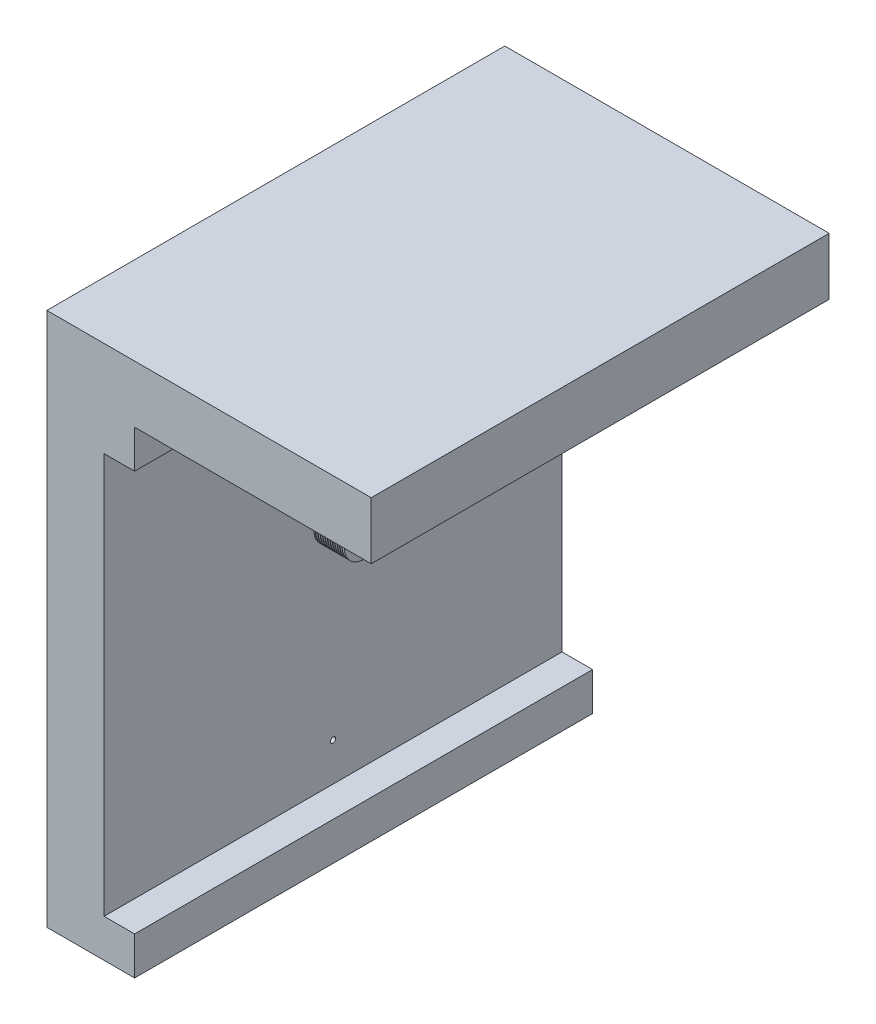
SolidWorks part; units mm, degrees
ref_plane "Front Plane" through (0, 0, 0) normal (0, 0, 1) x (1, 0, 0)
ref_plane "Top Plane" through (0, 0, 0) normal (0, 1, 0) x (1, 0, 0)
ref_plane "Right Plane" through (0, 0, 0) normal (1, 0, 0) x (0, 0, -1)
sketch "Sketch1" plane through (0, 0, 0) normal (0, 0, 1) x (1, 0, 0)
  line L0 (0, 0) -> (0, -70)
  line L1 (0, 0) -> (42.5, 0)
  line L2 (0, -70) -> (7.5, -70)
  line L3 (42.5, 0) -> (42.5, -7.5)
  line L4 (42.5, -7.5) -> (7.5, -7.5)
  line L5 (7.5, -7.5) -> (7.5, -70)
extrude "Boss-Extrude1" add sketch "Sketch1" along normal blind 60
sketch "Sketch3" plane through (0, 0, 0) normal (-1, 0, 0) x (0, 0, 1)
  line L1 (60, 0) -> (60, -70) construction
  line L2 (60, -60) -> (0, -60) construction
  line L3 (0, 0) -> (0, -70) construction
  circle A0 centre (30, -60) radius 0.35
extrude "Cut-Extrude1" cut sketch "Sketch3" against normal through all contours A0
sketch "Sketch5" plane through (7.5, 0, 0) normal (1, 0, 0) x (0, 0, -1)
  line L0 (-60, -70) -> (-60, -7.5) construction
  line L1 (0, -70) -> (-60, -70)
  line L2 (0, -70) -> (0, -65)
  line L3 (0, -65) -> (-60, -65)
  line L4 (-60, -70) -> (-60, -65)
  line L5 (0, -70) -> (0, -7.5) construction
  line L6 (-60, -7.5) -> (0, -7.5)
  line L7 (-60, -7.5) -> (-60, -12.5)
  line L8 (-60, -12.5) -> (0, -12.5)
  line L9 (0, -7.5) -> (0, -12.5)
  dimension "D1" = 5
  dimension "D2" = 5
extrude "Boss-Extrude2" add sketch "Sketch5" along normal blind 4
sketch "Sketch6" plane through (7.5, 0, 0) normal (1, 0, 0) x (0, 0, -1)
  line L0 (-30, -60) -> (-30, -35) construction
  circle A0 centre (-30, -35) radius 2.5
extrude "Boss-Extrude3" add sketch "Sketch6" along normal blind 4
thread "Thread1" pitch 0.3175 method cut profile "Thread Profile1" start angle 0, offset 0, length 5, pitch 0.3175, diameter 5
ref_plane "Plane1" through (11.5, -35, 32.5) normal (0, -1, 0) x (0, 0, 1)
sketch "Thread Profile1" plane through (11.5, -35, 32.5) normal (0, -1, 0) x (0, 0, 1)
  line L0 (0, 0) -> (0, 0.3175) construction
  line L11 (0, 0) -> (0, 0.2778)
  line L12 (0, 0.2778) -> (-0.1719, 0.1786)
  line L13 (-0.1719, 0.1786) -> (-0.1719, 0.0992)
  line L15 (-0.1719, 0.0992) -> (0, 0)
  line L17 (-0.1719, 0.1389) -> (0, 0.1389) construction
  point P2 (0, 0)
  dimension "Pitch" = 0.3175
  dimension "Profile_Angle" = 60
  dimension "Profile_Land" = 0.0794
  dimension "Profile_Height" = 0.1719
